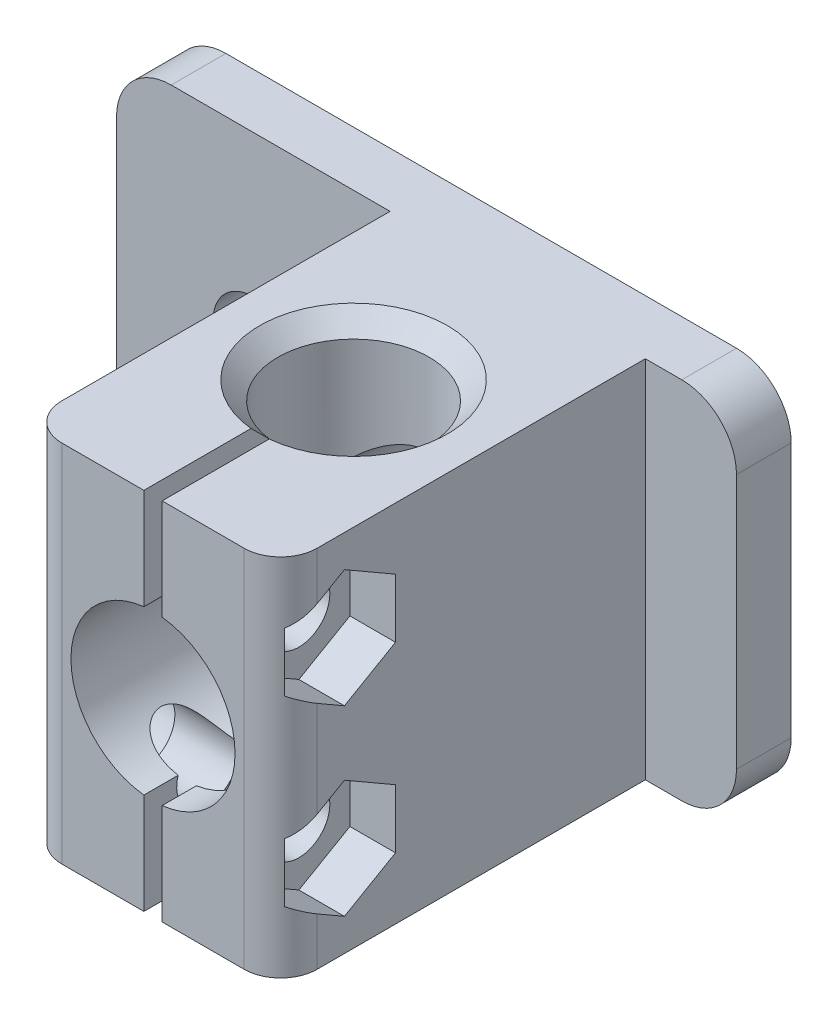
SolidWorks part; units mm, degrees
material "ABS"
ref_plane "Front Plane" through (0, 0, 0) normal (0, 0, 1) x (1, 0, 0)
ref_plane "Top Plane" through (0, 0, 0) normal (0, 1, 0) x (1, 0, 0)
ref_plane "Right Plane" through (0, 0, 0) normal (1, 0, 0) x (0, 0, -1)
sketch "Sketch1" plane through (0, 0, 0) normal (0, 0, 1) x (1, 0, 0)
  line L1 (-17, -10) -> (17, -10)
  line L2 (-17, -10) -> (-17, 10)
  line L3 (-17, 10) -> (17, 10)
  line L4 (17, -10) -> (17, 10)
  line L5 (-17, -10) -> (17, 10) construction
  line L6 (-17, 10) -> (17, -10) construction
  point P0 (0, 0)
  dimension "D1" = 20
  dimension "D2" = 34
extrude "Boss-Extrude1" add sketch "Sketch1" along normal blind 3
fillet "Fillet1" radius 3 4 edges at (17, -10, 1.5) (-17, -10, 1.5) (-17, 10, 1.5) (17, 10, 1.5)
sketch "Sketch2" plane through (0, 0, 3) normal (0, 0, 1) x (1, 0, 0)
  line L0 (14, 10) -> (-14, 10) construction
  line L1 (12, 10) -> (-2, 10)
  line L2 (12, 10) -> (12, -10)
  line L3 (12, -10) -> (-2, -10)
  line L4 (-2, 10) -> (-2, -10)
  line L5 (-14, -10) -> (14, -10) construction
  line L6 (17, -7) -> (17, 7) construction
  dimension "D1" = 14
  dimension "D2" = 5
extrude "Boss-Extrude2" add sketch "Sketch2" along normal blind 20
sketch "Sketch3" plane through (0, 10, 0) normal (0, 1, 0) x (1, 0, 0)
  line L0 (5, -12) -> (5, -23) construction
  line L1 (12, -23) -> (-2, -23) construction
  line L2 (4.5, -16.1198) -> (4.5, -23)
  line L3 (5.5, -16.1198) -> (5.5, -23)
  line L4 (4.5, -23) -> (5.5, -23)
  line L5 (14, 0) -> (-14, 0) construction
  arc A0 (5.5, -16.1198) -> (4.5, -16.1198) centre (5, -12) ccw
  dimension "D1" = 8.3
  dimension "D2" = 12
  dimension "D3" = 1
extrude "Cut-Extrude1" cut sketch "Sketch3" against normal through all
chamfer "Chamfer1" distance 1 angle 45 2 edges at (5, -10, 7.85) (5, 10, 7.85)
sketch "Sketch4" plane through (0, 0, 3) normal (0, 0, 1) x (1, 0, 0)
  line L0 (-2, 10) -> (-14, 10) construction
  line L1 (-17, 7) -> (-17, -7) construction
  circle A0 centre (-9.5, 0) radius 2.2
  point P4 (-8, 10)
  dimension "D1" = 4.4
  dimension "D2" = 10
  dimension "D3" = 7.5
extrude "Cut-Extrude2" cut sketch "Sketch4" against normal through all
sketch "Sketch5" plane through (12, 0, 0) normal (1, 0, 0) x (0, 0, -1)
  line L0 (0, -7) -> (0, 7) construction
  line L1 (-19.5, 5) -> (-19.5, -5) construction
  line L2 (-19.5, 0) -> (-23, 0) construction
  line L3 (-23, -10) -> (-23, 10) construction
  circle A0 centre (-19.5, 5) radius 1.7
  circle A1 centre (-19.5, -5) radius 1.7
  dimension "D1" = 3.4
  dimension "D2" = 10
  dimension "D3" = 19.5
extrude "Cut-Extrude3" cut sketch "Sketch5" against normal through all
fillet "Fillet2" radius 2 2 edges at (-2, 0, 23) (12, 0, 23)
sketch "Sketch6" plane through (12, 0, 0) normal (1, 0, 0) x (0, 0, -1)
  line L1 (-16.7, 3.3834) -> (-16.7, 6.6166)
  line L2 (-16.7, 6.6166) -> (-19.5, 8.2332)
  line L3 (-19.5, 8.2332) -> (-22.3, 6.6166)
  line L4 (-22.3, 6.6166) -> (-22.3, 3.3834)
  line L5 (-22.3, 3.3834) -> (-19.5, 1.7668)
  line L6 (-19.5, 1.7668) -> (-16.7, 3.3834)
  line L7 (-16.7, -3.3834) -> (-19.5, -1.7668)
  line L8 (-19.5, -1.7668) -> (-22.3, -3.3834)
  line L9 (-22.3, -3.3834) -> (-22.3, -6.6166)
  line L10 (-22.3, -6.6166) -> (-19.5, -8.2332)
  line L11 (-19.5, -8.2332) -> (-16.7, -6.6166)
  line L12 (-16.7, -6.6166) -> (-16.7, -3.3834)
  circle A0 centre (-19.5, 5) radius 2.8 construction
  circle A1 centre (-19.5, -5) radius 2.8 construction
  dimension "D1" = 5.6
extrude "Cut-Extrude4" cut sketch "Sketch6" against normal blind 2.5
sketch "Sketch7" plane through (-2, 0, 0) normal (-1, 0, 0) x (0, 0, 1)
  circle A0 centre (19.5, 5) radius 2.75
  circle A1 centre (19.5, -5) radius 2.75
  dimension "D1" = 5.5
extrude "Cut-Extrude5" cut sketch "Sketch7" against normal blind 3
sketch "Sketch8" plane through (0, 0, 23) normal (0, 0, 1) x (1, 0, 0)
  line L0 (-9.5, 0) -> (5, 0) construction
  circle A0 centre (5, 0) radius 2.2
  circle A1 centre (-9.5, 0) radius 2.2 construction
  dimension "D1" = 14.5
extrude "Cut-Extrude6" cut sketch "Sketch8" against normal through all
sketch "Sketch9" plane through (0, 0, 23) normal (0, 0, 1) x (1, 0, 0)
  circle A0 centre (5, 0) radius 4.5
  dimension "D1" = 9
extrude "Cut-Extrude7" cut sketch "Sketch9" against normal blind 21
